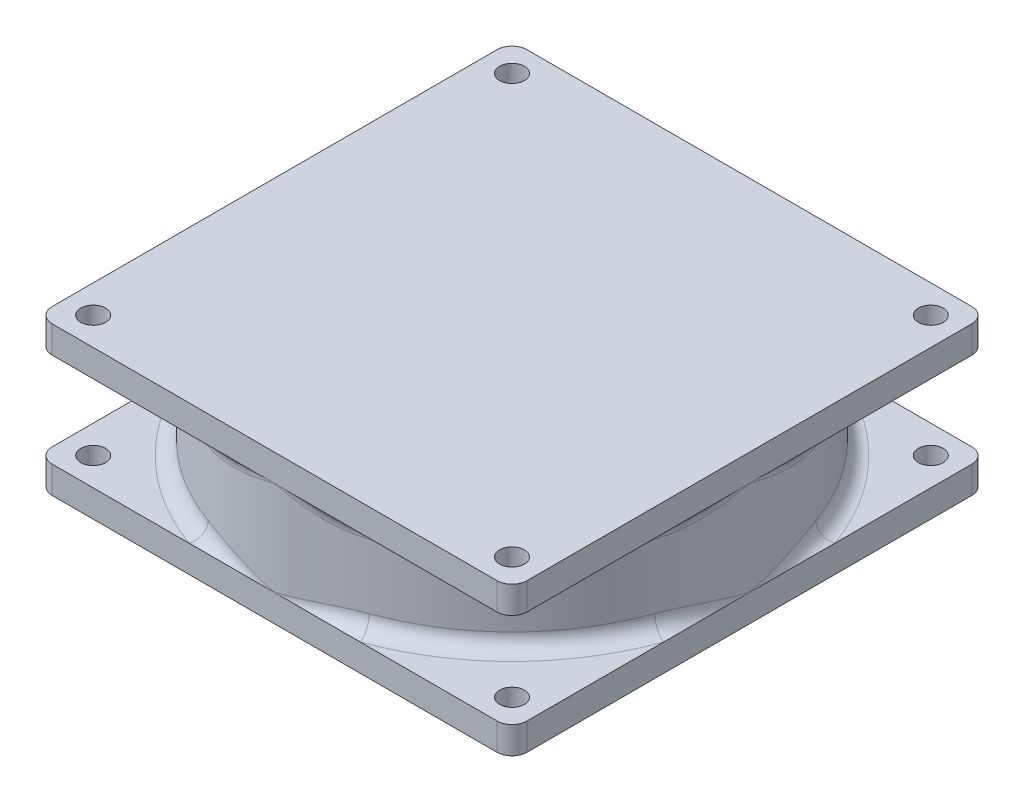
SolidWorks part; units mm, degrees
ref_plane "Front Plane" through (0, 0, 0) normal (0, 0, 1) x (1, 0, 0)
ref_plane "Top Plane" through (0, 0, 0) normal (0, 1, 0) x (1, 0, 0)
ref_plane "Right Plane" through (0, 0, 0) normal (1, 0, 0) x (0, 0, -1)
sketch "Sketch1" plane through (0, 0, 0) normal (0, 1, 0) x (1, 0, 0)
  line L1 (-40.25, 40.25) -> (40.25, 40.25)
  line L2 (-40.25, 40.25) -> (-40.25, -40.25)
  line L3 (-40.25, -40.25) -> (40.25, -40.25)
  line L4 (40.25, 40.25) -> (40.25, -40.25)
  line L5 (-40.25, 40.25) -> (40.25, -40.25) construction
  line L6 (-40.25, -40.25) -> (40.25, 40.25) construction
  point P0 (0, 0)
  dimension "D1" = 80.5
  dimension "D2" = 80.5
extrude "Boss-Extrude1" add sketch "Sketch1" along normal mid plane 25.2
sketch "Sketch2" plane through (0, 12.6, 0) normal (0, 1, 0) x (1, 0, 0)
  line L1 (-35.5, 35.5) -> (35.5, 35.5) construction
  line L2 (-35.5, 35.5) -> (-35.5, -35.5) construction
  line L3 (-35.5, -35.5) -> (35.5, -35.5) construction
  line L4 (35.5, 35.5) -> (35.5, -35.5) construction
  line L5 (-35.5, 35.5) -> (35.5, -35.5) construction
  line L6 (-35.5, -35.5) -> (35.5, 35.5) construction
  circle A0 centre (-35.5, 35.5) radius 2.1
  circle A1 centre (35.5, 35.5) radius 2.1
  circle A2 centre (35.5, -35.5) radius 2.1
  circle A3 centre (-35.5, -35.5) radius 2.1
  point P0 (0, 0)
  dimension "D1" = 4.2
  dimension "D2" = 71
  dimension "D3" = 71
extrude "Cut-Extrude1" cut sketch "Sketch2" against normal through all
fillet "Fillet1" radius 2.54 4 edges at (40.25, 0, -40.25) (40.25, 0, 40.25) (-40.25, 0, 40.25) (-40.25, 0, -40.25)
sketch "Sketch3" plane through (0, 0, 0) normal (1, 0, 0) x (0, 0, -1)
  line L0 (40.25, 8) -> (40.25, -8)
  line L1 (40.25, -8) -> (74.7293, -8)
  line L2 (74.7293, -8) -> (74.7293, 8)
  line L3 (74.7293, 8) -> (40.25, 8)
  line L4 (0, 0) -> (0, 50000) construction
  line L5 (40.25, 12.6) -> (40.25, -12.6) construction
  point P9 (40.25, 0)
  dimension "D1" = 34.4793
  dimension "D2" = 16
revolve "Cut-Revolve2" cut sketch "Sketch3" angle 360 about L4
fillet "Fillet2" radius 2.54 8 edges at (28.461, -8, -28.461) (-28.461, -8, -28.461) (-28.461, -8, 28.461) (-28.461, 8, -28.461) (28.461, 8, -28.461) (28.461, 8, 28.461) (-28.461, 8, 28.461) (28.461, -8, 28.461)
